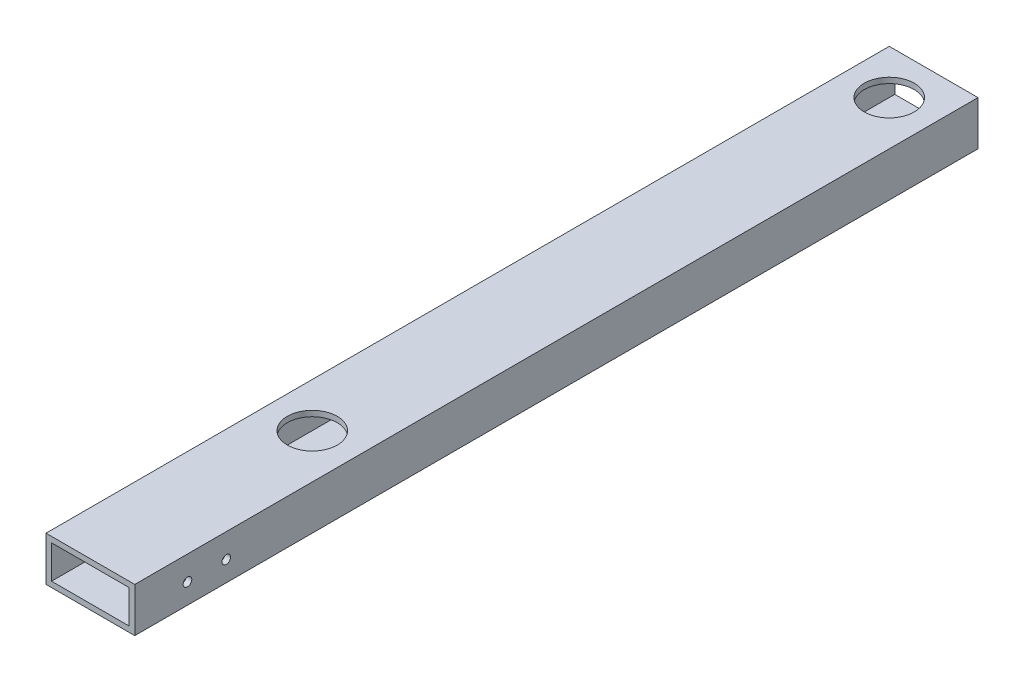
SolidWorks part; units mm, degrees
ref_plane "Front Plane" through (0, 0, 0) normal (0, 0, 1) x (1, 0, 0)
ref_plane "Top Plane" through (0, 0, 0) normal (0, 1, 0) x (1, 0, 0)
ref_plane "Right Plane" through (0, 0, 0) normal (1, 0, 0) x (0, 0, -1)
sketch "Sketch1" plane through (0, 0, 0) normal (0, 0, 1) x (1, 0, 0)
  line L1 (-25.4, -12.7) -> (25.4, -12.7)
  line L2 (-25.4, -12.7) -> (-25.4, 12.7)
  line L3 (-25.4, 12.7) -> (25.4, 12.7)
  line L4 (25.4, -12.7) -> (25.4, 12.7)
  line L5 (-25.4, -12.7) -> (25.4, 12.7) construction
  line L6 (-25.4, 12.7) -> (25.4, -12.7) construction
  point P0 (0, 0)
  dimension "D1" = 50.8
  dimension "D2" = 25.4
extrude "Boss-Extrude1" add sketch "Sketch1" along normal mid plane 482.6
sketch "Sketch2" plane through (0, 0, 241.3) normal (0, 0, 1) x (1, 0, 0)
  line L8 (22.225, -9.525) -> (22.225, 9.525)
  line L9 (22.225, 9.525) -> (-22.225, 9.525)
  line L10 (-22.225, 9.525) -> (-22.225, -9.525)
  line L11 (-22.225, -9.525) -> (22.225, -9.525)
  line L12 (22.225, -9.525) -> (22.225, 9.525)
  line L13 (22.225, 9.525) -> (-22.225, 9.525)
  line L14 (-22.225, 9.525) -> (-22.225, -9.525)
  line L15 (-22.225, -9.525) -> (22.225, -9.525)
  dimension "D1" = 3.175
extrude "Cut-Extrude1" cut sketch "Sketch2" against normal through all
sketch "Sketch5" plane through (0, 12.7, 0) normal (0, 1, 0) x (1, 0, 0)
  line L0 (25.4, -241.3) -> (25.4, 241.3) construction
  line L3 (0, 215.9) -> (0, -209.55) construction
  line L4 (22.225, -241.3) -> (-22.225, -241.3) construction
  circle A0 centre (0, -234.95) radius 2.4892 construction
  circle A1 centre (0, -209.55) radius 9.8488 construction
  circle A2 centre (0, -184.15) radius 2.4892 construction
  circle A3 centre (0, 215.9) radius 14.2875
  point P14 (0, -241.3)
  dimension "D1" = 28.575
  dimension "D2" = 25.4
  dimension "D5" = 4.9784
  dimension "D6" = 19.6977
  dimension "D7" = 4.9784
  dimension "D8" = 25.4
  dimension "D3" = 215.9
  dimension "D9" = 25.4
  dimension "D10" = 6.35
extrude "Cut-Extrude2" cut sketch "Sketch5" against normal blind 508
sketch "Sketch7" plane through (0, 12.7, 0) normal (0, 1, 0) x (1, 0, 0)
  line L0 (-25.4, -241.3) -> (-25.4, 241.3) construction
  line L1 (0, -139.7) -> (0, -88.9) construction
  line L2 (25.4, -241.3) -> (-25.4, -241.3) construction
  circle A0 centre (0, -114.3) radius 14.2875
  dimension "D1" = 28.575
  dimension "D2" = 127
  dimension "D3" = 25.4
extrude "Cut-Extrude4" cut sketch "Sketch7" against normal through all
sketch "Sketch8" plane through (25.4, 0, 0) normal (1, 0, 0) x (0, 0, -1)
  line L0 (-241.3, -12.7) -> (-241.3, 12.7) construction
  circle A0 centre (-222.25, 0) radius 1.9812
  circle A1 centre (-203.2, 0) radius 1.9812
  dimension "D1" = 2
  dimension "D2" = 19.05
hole_wizard "#10 (0.1935) Diameter Hole1" positions "Sketch12" profile "Sketch11" hole size "#10" standard "ANSI Inch" end condition through all
sketch "Sketch12" plane through (-25.4, 0, 0) normal (-1, 0, 0) x (0, 0, 1)
  line L0 (241.3, -12.7) -> (-241.3, -12.7) construction
  circle A0 centre (203.2, 0) radius 1.9812 construction
  point P0 (188.9125, -1.143)
  point P2 (211.1375, -1.143)
  dimension "D1" = 22.225
  dimension "D2" = 11.557
  dimension "D3" = 14.2875
sketch "Sketch11" plane through (-25.4, -1.143, 188.9125) normal (0, 1, 0) x (0, 0, 1)
  line L0 (0, 0) -> (0, 50.8)
  line L1 (0, 50.8) -> (2.4574, 50.8)
  line L2 (2.4574, 50.8) -> (2.4574, 0)
  line L5 (2.4574, 0) -> (0, 0)
  line L11 (0, -6.35) -> (0, 107.95) construction
  dimension "Thru Hole Dia." = 4.9149
  dimension "Thru Hole Depth" = 50.8
